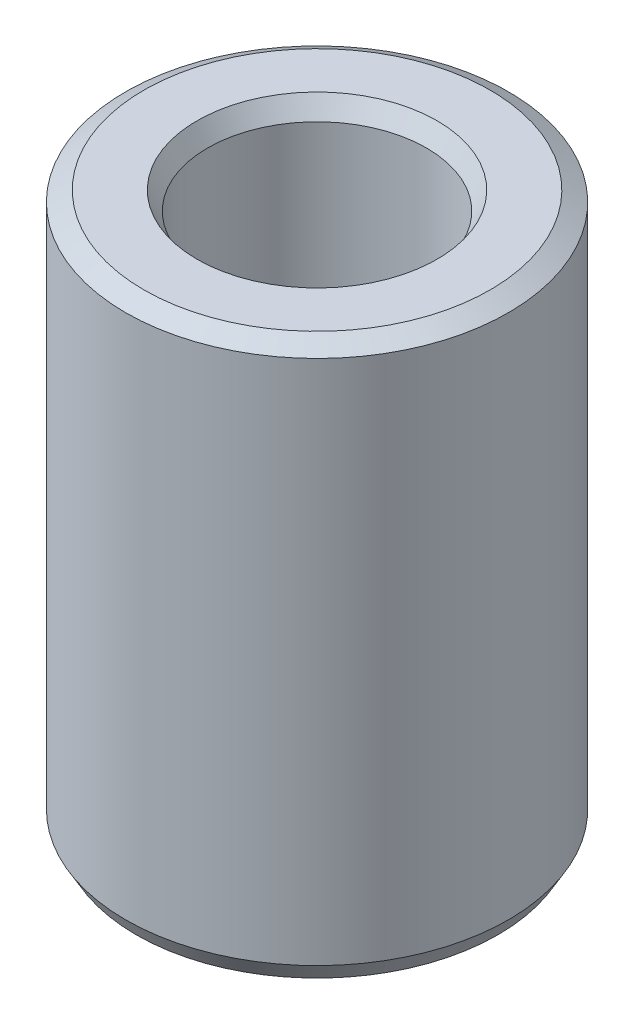
SolidWorks part; units mm, degrees
ref_plane "Front Plane" through (0, 0, 0) normal (0, 0, 1) x (1, 0, 0)
ref_plane "Top Plane" through (0, 0, 0) normal (0, 1, 0) x (1, 0, 0)
ref_plane "Right Plane" through (0, 0, 0) normal (1, 0, 0) x (0, 0, -1)
sketch "Sketch1" plane through (0, 0, 0) normal (0, 1, 0) x (1, 0, 0)
  circle A0 centre (0, 0) radius 25
  dimension "SLEEVE_OD" = 50
extrude "Boss-Extrude1" add sketch "Sketch1" along normal blind 72.4511
sketch "Sketch2" plane through (0, 0, 0) normal (0, 1, 0) x (1, 0, 0)
  circle A0 centre (0, 0) radius 14.2978
  dimension "BORE_D" = 28.5955
extrude "Cut-Extrude1" cut sketch "Sketch2" along normal through all
chamfer "Chamfer1" distance 1.3803 angle 60 4 edges at (0, 72.4511, 14.2978) (0, 0, 14.2978) (0, 0, 25) (0, 72.4511, 25) first distance on face at (0, 72.4511, 14.2978) first distance on face at (0, 0, 14.2978) first distance on face at (0, 72.4511, 25)
